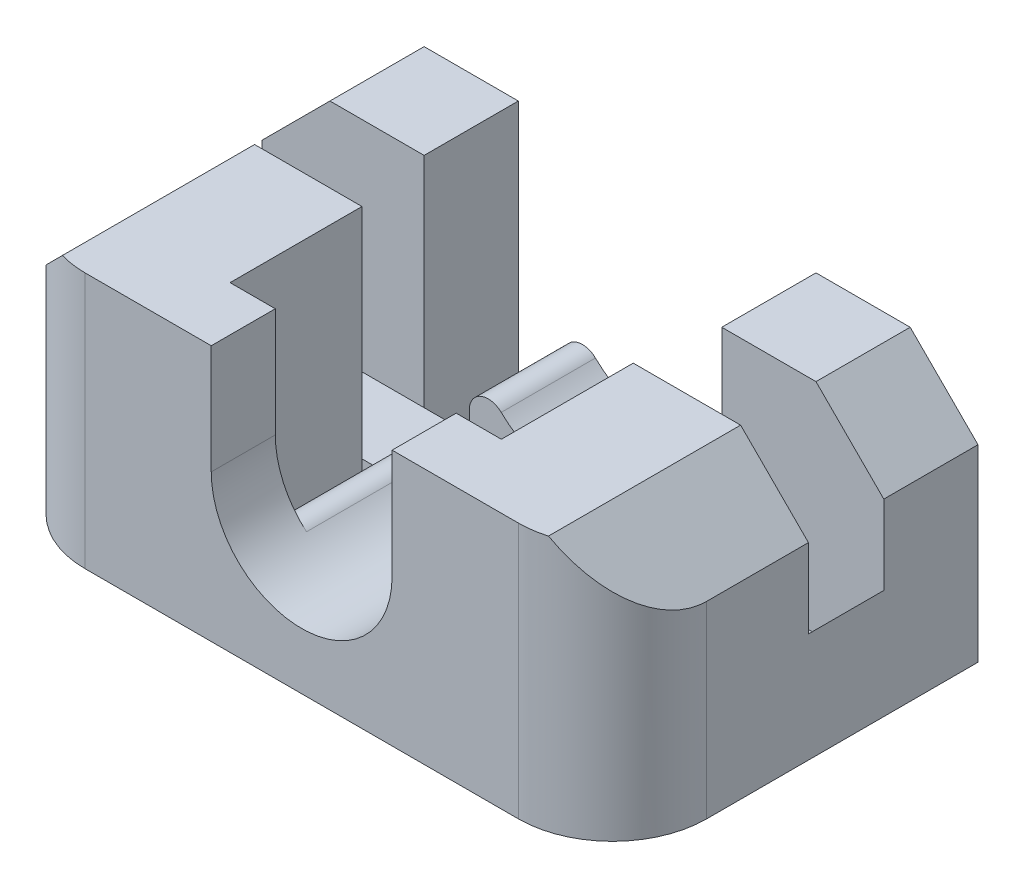
SolidWorks part; units mm, degrees
ref_plane "Front Plane" through (0, 0, 0) normal (0, 0, 1) x (1, 0, 0)
ref_plane "Top Plane" through (0, 0, 0) normal (0, 1, 0) x (1, 0, 0)
ref_plane "Right Plane" through (0, 0, 0) normal (1, 0, 0) x (0, 0, -1)
sketch "Sketch1" plane through (0, 0, 0) normal (0, 1, 0) x (1, 0, 0)
  line L1 (-8.25, 4.85) -> (8.25, 4.85)
  line L2 (-8.25, 4.85) -> (-8.25, -4.85)
  line L3 (-8.25, -4.85) -> (8.25, -4.85)
  line L4 (8.25, 4.85) -> (8.25, -4.85)
  line L5 (-8.25, 4.85) -> (8.25, -4.85) construction
  line L6 (-8.25, -4.85) -> (8.25, 4.85) construction
  point P0 (0, 0)
  dimension "D1" = 16.5
  dimension "D2" = 9.7
extrude "Boss-Extrude1" add sketch "Sketch1" along normal blind 6.8
sketch "Sketch2" plane through (0, 6.8, 0) normal (0, 1, 0) x (1, 0, 0)
  line L0 (-8.25, 1.35) -> (8.25, 1.35) construction
  line L3 (-8.25, 4.85) -> (-8.25, -4.85) construction
  line L4 (-8.25, 2.35) -> (8.25, 2.35)
  line L5 (-8.25, 2.35) -> (-8.25, 0.35)
  line L6 (-8.25, 0.35) -> (8.25, 0.35)
  line L7 (8.25, 2.35) -> (8.25, 0.35)
  line L8 (-8.25, 2.35) -> (8.25, 0.35) construction
  line L9 (-8.25, 0.35) -> (8.25, 2.35) construction
  line L10 (8.25, -4.85) -> (8.25, 4.85) construction
  line L11 (8.25, 4.85) -> (-8.25, 4.85) construction
  line L12 (0, 4.85) -> (0, -4.85) construction
  line L13 (-8.25, -4.85) -> (8.25, -4.85) construction
  point P6 (0, 1.35)
  dimension "D1" = 16.5
  dimension "D2" = 2
  dimension "D3" = 2.5
extrude "Cut-Extrude1" cut sketch "Sketch2" against normal blind 5.8
sketch "Sketch3" plane through (0, 0, -4.85) normal (0, 0, -1) x (-1, 0, 0)
  line L0 (0, 6.8) -> (0, 0) construction
  line L1 (-8.25, 6.8) -> (8.25, 6.8) construction
  line L2 (-8.25, 0) -> (8.25, 0) construction
  line L3 (-8.25, 1) -> (8.25, 1) construction
  line L4 (-8.25, 6.8) -> (-8.25, 0) construction
  line L5 (8.25, 6.8) -> (8.25, 0) construction
  line L6 (-8.25, 1) -> (8.25, 1) construction
  line L7 (-8.25, 6.8) -> (8.25, 1) construction
  line L8 (8.25, 6.8) -> (-8.25, 1) construction
  line L9 (-2.75, 3.9) -> (-2.75, 6.8)
  line L10 (2.75, 3.9) -> (2.75, 6.8)
  circle A0 centre (0, 3.9) radius 2.75
  line M5 (8.25, 6.8) -> (-8.25, 6.8)
  dimension "D1" = 5.5
extrude "Cut-Extrude2" cut sketch "Sketch3" against normal up to next contours A0 | A0 L10 L9 M5 region at (2.6878, 5.35, -4.85) region at (0, 3.9, -4.85)
sketch "Sketch4" plane through (0, 0, 4.85) normal (0, 0, 1) x (1, 0, 0)
  line L0 (0, 0) -> (0, 6.8) construction
  line L1 (-8.25, 6.8) -> (8.25, 6.8) construction
  line L3 (-2.4, 3.9) -> (2.4, 3.9)
  line L4 (-2.4, 3.9) -> (-2.4, 6.8)
  line L5 (-2.4, 6.8) -> (2.4, 6.8)
  line L6 (2.4, 3.9) -> (2.4, 6.8)
  circle A0 centre (0, 3.9) radius 2.4
  arc A1 (-2.75, 3.9) -> (2.75, 3.9) centre (0, 3.9) ccw construction
  line M4 (8.25, 6.8) -> (-8.25, 6.8)
  dimension "D1" = 4.8
extrude "Cut-Extrude3" cut sketch "Sketch4" against normal up to next contours L0 A0 L3 | A0 L0 L3 | L3 L0 A0 | L0 L3 A0 | L0 A0 L6 M4 | A0 L0 L5 L4 region at (-1.0186, 2.8814, 4.85) region at (1.0186, 2.8814, 4.85) region at (-1.0186, 4.9186, 4.85) region at (1.0186, 4.9186, 4.85) region at (-1.5369, 6.1511, 4.85) region at (1.5369, 6.1511, 4.85)
sketch "Sketch5" plane through (0, 6.8, 0) normal (0, 1, 0) x (1, 0, 0)
  line L0 (-2.75, 2.35) -> (-8.25, 2.35) construction
  line L1 (-2.75, 4.85) -> (-3.95, 4.85)
  line L2 (-2.75, 4.85) -> (-2.75, 2.35)
  line L3 (-2.75, 2.35) -> (-3.95, 2.35)
  line L4 (-3.95, 4.85) -> (-3.95, 2.35)
  line L5 (8.25, 2.35) -> (2.75, 2.35) construction
  line L6 (2.75, 4.85) -> (3.95, 4.85)
  line L7 (2.75, 4.85) -> (2.75, 2.35)
  line L8 (2.75, 2.35) -> (3.95, 2.35)
  line L9 (3.95, 4.85) -> (3.95, 2.35)
  line L11 (-2.4, 0.35) -> (-3.6, 0.35)
  line L12 (-2.4, 0.35) -> (-2.4, -3.15)
  line L13 (-2.4, -3.15) -> (-3.6, -3.15)
  line L14 (-3.6, 0.35) -> (-3.6, -3.15)
  line L15 (2.4, 0.35) -> (3.6, 0.35)
  line L16 (2.4, 0.35) -> (2.4, -3.15)
  line L17 (2.4, -3.15) -> (3.6, -3.15)
  line L18 (3.6, 0.35) -> (3.6, -3.15)
  dimension "D1" = 1.2
  dimension "D2" = 3.5
extrude "Cut-Extrude4" cut sketch "Sketch5" against normal through all
fillet "Fillet1" radius 0.5 4 edges at (2.4, 3.9, 1.4) (-2.4, 3.9, 1.4) (-2.75, 3.9, -3.6) (2.75, 3.9, -3.6)
sketch "Sketch6" plane through (0, 6.8, 0) normal (0, 1, 0) x (1, 0, 0)
  line L1 (-8.25, -4.85) -> (8.25, -4.85)
  line L2 (-8.25, -4.85) -> (-8.25, 4.85)
  line L3 (-8.25, 4.85) -> (8.25, 4.85)
  line L4 (8.25, -4.85) -> (8.25, 4.85)
extrude "Cut-Extrude5" [suppressed] cut sketch "Sketch6" against normal up to vertex up to point (2.4, 3.9, 3.15)
sketch "Sketch7" plane through (0, 0, -2.35) normal (0, 0, 1) x (1, 0, 0)
  line L0 (-6.35, 1) -> (-8.25, 2.9)
  line L1 (-3.95, 1) -> (-8.25, 1) construction
  line L2 (-8.25, 1) -> (-8.25, 6.8) construction
  line L3 (0, 0) -> (0, 3.9) construction
  line L4 (-8.25, 2.9) -> (-8.25, 1)
  line L5 (-8.25, 6.8) -> (-8.25, 0) construction
  line L6 (-8.25, 1) -> (-6.35, 1)
  line L7 (8.25, 2.9) -> (8.25, 1)
  line L8 (6.35, 1) -> (8.25, 2.9)
  line L9 (8.25, 1) -> (6.35, 1)
  dimension "D1" = 45
  dimension "D2" = 1.9
extrude "Boss-Extrude2" add sketch "Sketch7" along normal up to surface (2 mm away) up to face at (-5.925, 3.9, -0.35)
chamfer "Chamfer1" distance 1.8 angle 45 4 edges at (-8.25, 6.8, -3.6) (-8.25, 6.8, 2.25) (8.25, 6.8, -3.6) (8.25, 6.8, 2.25)
fillet "Fillet4" radius 2.5 2 edges at (8.25, 2.5, 4.85) (-8.25, 2.5, 4.85)
